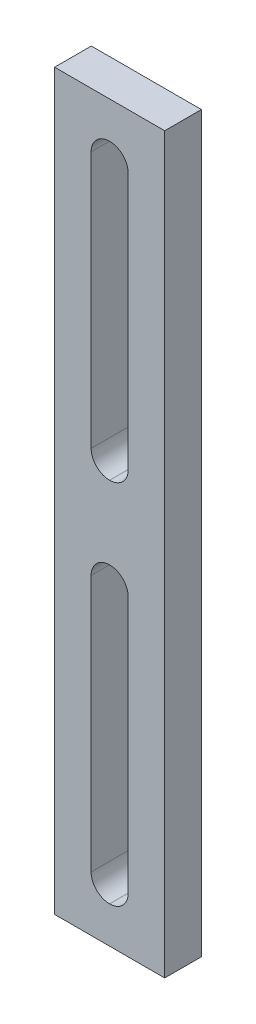
SolidWorks part; units mm, degrees
ref_plane "Спереди" through (0, 0, 0) normal (0, 0, 1) x (1, 0, 0)
ref_plane "Сверху" through (0, 0, 0) normal (0, 1, 0) x (1, 0, 0)
ref_plane "Справа" through (0, 0, 0) normal (1, 0, 0) x (0, 0, -1)
sketch "Эскиз1" plane through (0, 0, 0) normal (0, 0, 1) x (1, 0, 0)
  line L1 (0, 0) -> (30, 0)
  line L2 (0, 0) -> (0, 200)
  line L3 (0, 200) -> (30, 200)
  line L4 (30, 0) -> (30, 200)
extrude "Бобышка-Вытянуть1" add sketch "Эскиз1" along normal blind 10
sketch "Эскиз2" plane through (0, 0, 10) normal (0, 0, 1) x (1, 0, 0)
  line L0 (14.95, 190) -> (15.05, 190)
  line L1 (14.95, 90) -> (15.05, 90)
  line L2 (9.95, 85) -> (9.95, 15)
  line L3 (14.95, 10) -> (15.05, 10)
  line L4 (20.05, 85) -> (20.05, 15)
  line L5 (9.95, 90) -> (20.05, 10) construction
  line L6 (9.95, 10) -> (20.05, 90) construction
  line L7 (9.95, 185) -> (9.95, 115)
  line L8 (14.95, 110) -> (15.05, 110)
  line L9 (20.05, 185) -> (20.05, 115)
  line L10 (9.95, 190) -> (20.05, 110) construction
  line L11 (9.95, 110) -> (20.05, 190) construction
  arc A0 (9.95, 15) -> (14.95, 10) centre (14.95, 15) ccw
  arc A1 (15.05, 10) -> (20.05, 15) centre (15.05, 15) ccw
  arc A2 (14.95, 90) -> (9.95, 85) centre (14.95, 85) ccw
  arc A3 (15.05, 90) -> (20.05, 85) centre (15.05, 85) cw
  arc A4 (9.95, 115) -> (14.95, 110) centre (14.95, 115) ccw
  arc A5 (15.05, 110) -> (20.05, 115) centre (15.05, 115) ccw
  arc A6 (14.95, 190) -> (9.95, 185) centre (14.95, 185) ccw
  arc A7 (15.05, 190) -> (20.05, 185) centre (15.05, 185) cw
  point P0 (15, 50)
  point P5 (15, 150)
  dimension "D1" = 5
  dimension "D2" = 2
extrude "Вырез-Вытянуть1" cut sketch "Эскиз2" against normal through all
